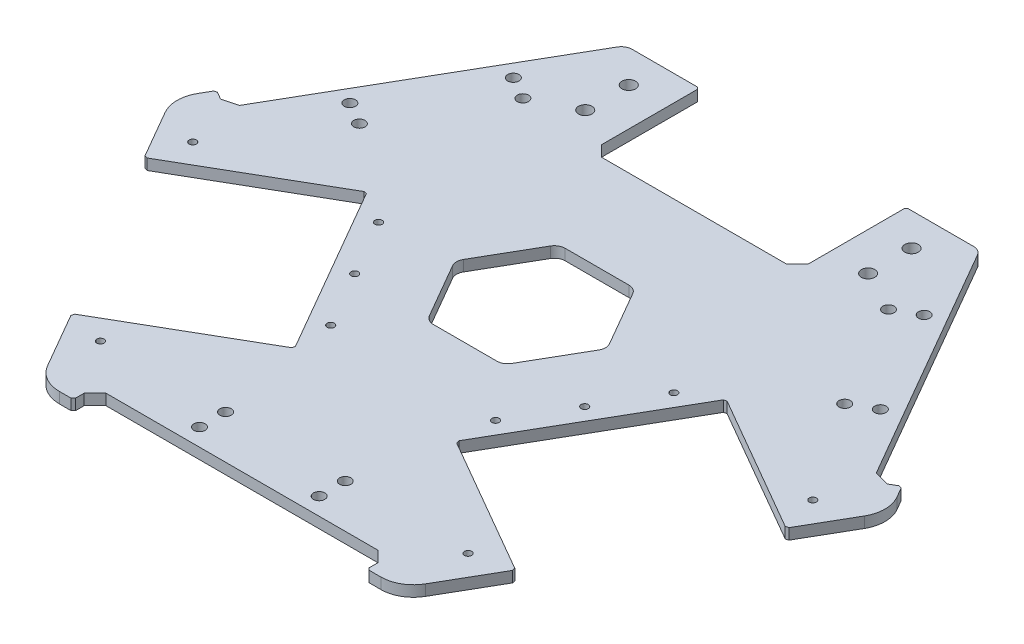
SolidWorks part; units mm, degrees
material "5052-O"
ref_plane "前基準面" through (0, 0, 0) normal (0, 0, 1) x (1, 0, 0)
ref_plane "上基準面" through (0, 0, 0) normal (0, 1, 0) x (1, 0, 0)
ref_plane "右基準面" through (0, 0, 0) normal (1, 0, 0) x (0, 0, -1)
sketch "草圖1" plane through (0, 0, 0) normal (0, 1, 0) x (1, 0, 0)
  line L1 (82.5, 142.8942) -> (-82.5, 142.8942)
  line L2 (-82.5, 142.8942) -> (-165, 0)
  line L3 (-165, 0) -> (-82.5, -142.8942)
  line L4 (-82.5, -142.8942) -> (82.5, -142.8942)
  line L5 (82.5, -142.8942) -> (165, 0)
  line L6 (165, 0) -> (82.5, 142.8942)
  circle A0 centre (0, 0) radius 142.8942 construction
  dimension "D1" = 165
extrude "填料-伸長1" add sketch "草圖1" along normal blind 5
sketch "草圖2" plane through (0, 5, 0) normal (0, 1, 0) x (1, 0, 0)
  line L0 (-82.5, -142.8942) -> (82.5, -142.8942) construction
  line L1 (-67.5, -132.8942) -> (67.5, -132.8942)
  line L2 (-67.5, -132.8942) -> (-67.5, -142.8942)
  line L3 (-67.5, -142.8942) -> (67.5, -142.8942)
  line L4 (67.5, -132.8942) -> (67.5, -142.8942)
  point P4 (0, -142.8942)
  dimension "D1" = 135
  dimension "D2" = 10
extrude "除料-伸長1" cut sketch "草圖2" against normal through all
ref_axis "基準軸1" through (0, -0.25, 0) along (0, 1, 0)
sketch "草圖8" plane through (0, 5, 0) normal (0, 1, 0) x (1, 0, 0)
  line L0 (-27.5, -124.8942) -> (27.5, -124.8942) construction
  line L1 (0, -124.8942) -> (0, -132.8942) construction
  line L2 (67.5, -132.8942) -> (-67.5, -132.8942) construction
  line L3 (-27.5, -112.8942) -> (27.5, -112.8942) construction
  line L4 (0, -112.8942) -> (0, -124.8942) construction
  circle A0 centre (-27.5, -124.8942) radius 2.6
  circle A1 centre (27.5, -124.8942) radius 2.6
  circle A2 centre (-27.5, -112.8942) radius 2.6
  circle A3 centre (27.5, -112.8942) radius 2.6
  dimension "D3" = 5.2
  dimension "D1" = 55
  dimension "D2" = 8
  dimension "D4" = 12
extrude "除料-伸長6" cut sketch "草圖8" against normal through all
pattern_circular "環狀複製排列1" count 3 over 360 about axis through (0, -0.25, 0) along (0, 1, 0) of "除料-伸長1", "除料-伸長6"
sketch "草圖23" plane through (0, 5, 0) normal (0, 1, 0) x (1, 0, 0)
  line L10 (-81.3397, 124.9038) -> (81.3397, 124.9038)
extrude "除料-伸長17" cut sketch "草圖23" against normal through all and the other way through all
sketch "草圖4" plane through (0, 5, 0) normal (0, 1, 0) x (1, 0, 0)
  line L1 (17.5, 30.3109) -> (-17.5, 30.3109)
  line L2 (-17.5, 30.3109) -> (-35, 0)
  line L3 (-35, 0) -> (-17.5, -30.3109)
  line L4 (-17.5, -30.3109) -> (17.5, -30.3109)
  line L5 (17.5, -30.3109) -> (35, 0)
  line L6 (35, 0) -> (17.5, 30.3109)
  circle A0 centre (0, 0) radius 30.3109 construction
  dimension "D1" = 35
extrude "除料-伸長3" cut sketch "草圖4" against normal through all
sketch "草圖5" plane through (0, 5, 0) normal (0, 1, 0) x (1, 0, 0)
  line L0 (-147.5, -30.3109) -> (-102, -109.1192)
  line L1 (-147.5, -30.3109) -> (-82.5481, 7.1891)
  line L2 (-102, -109.1192) -> (-37.0481, -71.6192)
  line L3 (-82.5481, 7.1891) -> (-37.0481, -71.6192)
  line L4 (-165, 0) -> (-82.5, -142.8942) construction
  dimension "D1" = 75
  dimension "D2" = 91
  dimension "35" = 35
extrude "除料-伸長4" cut sketch "草圖5" against normal through all
sketch "草圖9" plane through (0, 5, 0) normal (0, 1, 0) x (1, 0, 0)
  line L0 (-59.7981, -32.215) -> (-113.4917, -63.215) construction
  line L1 (-37.0481, -71.6192) -> (-82.5481, 7.1891) construction
  line L2 (-113.4917, -63.215) -> (-84.4917, -113.4445) construction
  line L3 (-113.4917, -63.215) -> (-142.4917, -12.9856) construction
  circle A0 centre (-84.4917, -113.4445) radius 1.65
  circle A1 centre (-142.4917, -12.9856) radius 1.65
  dimension "D2" = 3.3
  dimension "D1" = 58
  dimension "D3" = 62
  dimension "D4" = 58
extrude "除料-伸長7" cut sketch "草圖9" against normal through all
mirror "鏡射1" about plane through (0, 0, 0) normal (1, 0, 0) of "除料-伸長4", "除料-伸長7"
fillet "圓角1" radius 15 4 edges at (165, 2.5, 0) (82.5, 2.5, 142.8942) (-165, 2.5, 0) (-82.5, 2.5, 142.8942)
sketch "草圖34" plane through (0, 5, 0) normal (0, 1, 0) x (1, 0, 0)
  line L0 (0, 124.9038) -> (0, 30.3109) construction
  line L2 (17.5, 30.3109) -> (-17.5, 30.3109) construction
  line L3 (81.3397, 124.9038) -> (-81.3397, 124.9038) construction
  circle A0 centre (-65, 109.9038) radius 3.1
  dimension "D1" = 6.2
  dimension "D2" = 15
  dimension "D3" = 65
extrude "除料-伸長18" cut sketch "草圖34" against normal through all
pattern_linear "直線複製排列1" count 2 spacing 20 along (0, 0, 1) of "除料-伸長18"
sketch "草圖35" plane through (0, 5, 0) normal (0, 1, 0) x (1, 0, 0)
  line L2 (47.5, 124.9038) -> (47.5, 74.9038)
  line L3 (47.5, 74.9038) -> (-47.5, 74.9038)
  line L4 (-47.5, 124.9038) -> (-47.5, 74.9038)
  line L5 (81.3397, 124.9038) -> (-81.3397, 124.9038) construction
  line L6 (47.5, 124.9038) -> (-47.5, 124.9038)
  line L7 (17.5, 30.3109) -> (-17.5, 30.3109) construction
  point P4 (0, 74.9038)
  point P9 (0, 30.3109)
  dimension "D1" = 95
  dimension "D2" = 50
extrude "除料-伸長19" cut sketch "草圖35" against normal through all
chamfer "導角2" distance 1 angle 45 14 edges at (-37.0481, 2.5, 71.6192) (-82.5481, 2.5, -7.1891) (-157.5, 2.5, -12.9904) (157.5, 2.5, -12.9904) (147.5, 2.5, 30.3109) (82.5481, 2.5, -7.1891) (37.0481, 2.5, 71.6192) (102, 2.5, 109.1192) (67.5, 2.5, 142.8942) (-67.5, 2.5, 142.8942) (-102, 2.5, 109.1192) (-147.5, 2.5, 30.3109) (-47.5, 2.5, -124.9038) (47.5, 2.5, -124.9038)
chamfer "導角4" distance 5 angle 45 6 edges at (148.8397, 2.5, -7.9904) (67.5, 2.5, 132.8942) (-67.5, 2.5, 132.8942) (-148.8397, 2.5, -7.9904) (47.5, 2.5, -74.9038) (-47.5, 2.5, -74.9038)
fillet "圓角2" radius 5 2 edges at (-81.3397, 2.5, -124.9038) (81.3397, 2.5, -124.9038)
fillet "圓角3" radius 5 6 edges at (17.5, 2.5, 30.3109) (35, 2.5, 0) (17.5, 2.5, -30.3109) (-17.5, 2.5, 30.3109) (-35, 2.5, 0) (-17.5, 2.5, -30.3109)
sketch "草圖36" plane through (0, 5, 0) normal (0, 1, 0) x (1, 0, 0)
  line L0 (-67.8699, -2.2343) -> (-52.8699, -28.215) construction
  line L1 (-37.5481, -70.7532) -> (-82.0481, 6.3231) construction
  line L2 (-37.8699, -54.1958) -> (-52.8699, -28.215) construction
  line L3 (-52.8699, -28.215) -> (-59.7981, -32.215) construction
  circle A0 centre (-52.8699, -28.215) radius 1.25
  circle A1 centre (-37.8699, -54.1958) radius 1.25
  circle A2 centre (-67.8699, -2.2343) radius 1.25
  point P7 (-45.3699, -41.2054)
  point P10 (-59.7981, -32.215)
  dimension "D3" = 2.5
  dimension "D1" = 30
  dimension "D2" = 30
  dimension "D4" = 8
hole_wizard "M4x0.7 螺紋孔4" positions "草圖40" profile "草圖41" tap size "M4x0.7" standard "Ansi Metric" end condition through all
sketch "草圖40" plane through (0, 5, 0) normal (0, 1, 0) x (1, 0, 0)
  point P0 (-67.8699, -2.2343)
  point P3 (-52.8699, -28.215)
  point P6 (-37.8699, -54.1958)
sketch "草圖41" plane through (-67.8699, 5, 2.2343) normal (1, 0, 0) x (0, 0, 1)
  line L0 (0, 0) -> (0, 5)
  line L1 (0, 5) -> (1.65, 5)
  line L2 (1.65, 5) -> (1.65, 0)
  line L5 (1.65, 0) -> (0, 0)
  line L11 (0, -6.35) -> (0, 107.95) construction
  dimension "貫穿螺孔鑽直徑" = 3.3
  dimension "貫穿螺孔鑽深度" = 5
cosmetic thread "鑽孔螺紋9" parameters "D2"=4
cosmetic thread "鑽孔螺紋10" parameters "D2"=4
cosmetic thread "鑽孔螺紋11" parameters "D2"=4
mirror "鏡射2" about plane through (0, 0, 0) normal (1, 0, 0) of "M4x0.7 螺紋孔4", "直線複製排列1"
